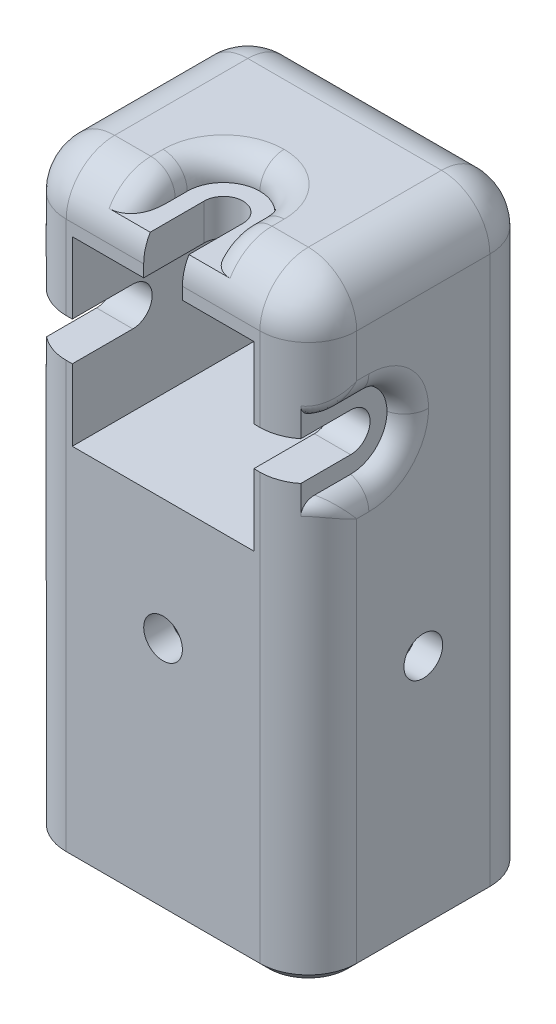
SolidWorks part; units mm, degrees
ref_plane "Front Plane" through (0, 0, 0) normal (0, 0, 1) x (1, 0, 0)
ref_plane "Top Plane" through (0, 0, 0) normal (0, 1, 0) x (1, 0, 0)
ref_plane "Right Plane" through (0, 0, 0) normal (1, 0, 0) x (0, 0, -1)
sketch "Sketch1" plane through (0, 0, 0) normal (0, 1, 0) x (1, 0, 0)
  line L1 (0, 0) -> (24, 0)
  line L2 (0, 0) -> (0, 19)
  line L3 (0, 19) -> (24, 19)
  line L4 (24, 0) -> (24, 19)
  dimension "D1" = 24
  dimension "D2" = 19
extrude "Boss-Extrude1" add sketch "Sketch1" along normal blind 50
sketch "Sketch2" plane through (0, 0, 0) normal (0, 0, 1) x (1, 0, 0)
  line L0 (0, 0) -> (24, 0) construction
  line L1 (4.5, 45) -> (19.5, 45)
  line L2 (4.5, 45) -> (4.5, 30)
  line L3 (4.5, 30) -> (19.5, 30)
  line L4 (19.5, 45) -> (19.5, 30)
  line L5 (0, 50) -> (24, 50) construction
  point P6 (12, 45)
  point P9 (12, 50)
  dimension "D1" = 15
  dimension "D2" = 30
extrude "Cut-Extrude1" cut sketch "Sketch2" against normal blind 16
sketch "Sketch3" plane through (0, 0, -16) normal (0, 0, 1) x (1, 0, 0)
  line L0 (19.5, 45) -> (4.5, 45) construction
  line L1 (19.5, 30) -> (19.5, 45) construction
  circle A0 centre (12, 37.5) radius 1.6
  point P5 (12, 45)
  point P9 (19.5, 37.5)
  dimension "D1" = 3.2
extrude "Cut-Extrude2" cut sketch "Sketch3" against normal up to next
sketch "Sketch4" plane through (0, 0, 0) normal (0, -1, 0) x (1, 0, 0)
  line L5 (0, 0) -> (24, 0) construction
  line L11 (24, 0) -> (24, -19) construction
  line L48 (24, -19) -> (0, -19) construction
  line L49 (8.95, -16.8) -> (15.05, -16.8)
  line L50 (8.95, -16.8) -> (8.95, -13.8)
  line L51 (8.95, -13.8) -> (15.05, -13.8)
  line L52 (15.05, -16.8) -> (15.05, -13.8)
  line L53 (2.2, -12.55) -> (5.2, -12.55)
  line L54 (2.2, -12.55) -> (2.2, -6.45)
  line L55 (2.2, -6.45) -> (5.2, -6.45)
  line L56 (5.2, -12.55) -> (5.2, -6.45)
  line L57 (8.95, -5.2) -> (15.05, -5.2)
  line L58 (8.95, -5.2) -> (8.95, -2.2)
  line L59 (8.95, -2.2) -> (15.05, -2.2)
  line L60 (15.05, -5.2) -> (15.05, -2.2)
  line L61 (18.8, -12.55) -> (21.8, -12.55)
  line L62 (18.8, -12.55) -> (18.8, -6.45)
  line L63 (18.8, -6.45) -> (21.8, -6.45)
  line L64 (21.8, -12.55) -> (21.8, -6.45)
  line L65 (0, -19) -> (0, 0) construction
  point P20 (12, -16.8)
  point P21 (12, -5.2)
  point P24 (12, -19)
  point P25 (2.2, -9.5)
  point P26 (18.8, -9.5)
  point P37 (24, -9.5)
  dimension "D1" = 6.1
  dimension "D2" = 3
  dimension "D3" = 2.2
  dimension "D4" = 2.2
  dimension "D5" = 2.2
  dimension "D6" = 2.2
extrude "Cut-Extrude3" cut sketch "Sketch4" against normal blind 23
sketch "Sketch5" plane through (0, 0, -19) normal (0, 0, -1) x (-1, 0, 0)
  line L0 (-24, 0) -> (0, 0) construction
  circle A0 centre (-12, 20) radius 1.6
  point P5 (-12, 0)
  dimension "D1" = 3.2
  dimension "D2" = 20
extrude "Cut-Extrude4" cut sketch "Sketch5" against normal through all
sketch "Sketch6" plane through (0, 0, 0) normal (-1, 0, 0) x (0, 0, 1)
  line L0 (-19, 0) -> (0, 0) construction
  circle A0 centre (-9.5, 20) radius 1.6
  point P5 (-9.5, 0)
  dimension "D1" = 3.2
  dimension "D2" = 20
extrude "Cut-Extrude5" cut sketch "Sketch6" against normal through all
sketch "Sketch7" plane through (0, 0, 0) normal (0, 0, 1) x (1, 0, 0)
  line L0 (0, 50) -> (0, 0) construction
  line L1 (0, 40.5) -> (1.5, 40.5)
  line L2 (0, 40.5) -> (0, 34.5)
  line L3 (0, 34.5) -> (1.5, 34.5)
  line L4 (1.5, 40.5) -> (1.5, 34.5)
  line L5 (24, 50) -> (24, 0) construction
  line L6 (24, 40.5) -> (22.5, 40.5)
  line L7 (24, 40.5) -> (24, 34.5)
  line L8 (24, 34.5) -> (22.5, 34.5)
  line L9 (22.5, 40.5) -> (22.5, 34.5)
  line L10 (0, 50) -> (24, 50) construction
  line L11 (9, 50) -> (15, 50)
  line L12 (9, 50) -> (9, 48)
  line L13 (9, 48) -> (15, 48)
  line L14 (15, 50) -> (15, 48)
  line L15 (19.5, 45) -> (4.5, 45) construction
  line L16 (4.5, 45) -> (4.5, 30) construction
  line L17 (19.5, 30) -> (19.5, 45) construction
  point P24 (22.5, 37.5)
  point P25 (19.5, 37.5)
  point P26 (1.5, 37.5)
  point P27 (4.5, 37.5)
  point P28 (12, 45)
  point P29 (12, 48)
  dimension "D1" = 3
  dimension "D2" = 3
  dimension "D3" = 3
  dimension "D4" = 6
extrude "Cut-Extrude6" cut sketch "Sketch7" against normal blind 8
sketch "Sketch8" plane through (1.5, 0, 0) normal (-1, 0, 0) x (0, 0, 1)
  line L0 (-5, 35.9) -> (0, 35.9)
  line L1 (0, 34.5) -> (0, 40.5) construction
  line L2 (0, 35.9) -> (0, 39.1)
  line L3 (0, 39.1) -> (-5, 39.1)
  arc A0 (-5, 39.1) -> (-5, 35.9) centre (-5, 37.5) ccw
  point P1 (0, 37.5)
  point P6 (0, 37.5)
  dimension "D1" = 1.6
  dimension "D2" = 5
extrude "Cut-Extrude7" cut sketch "Sketch8" against normal through all
sketch "Sketch9" plane through (0, 48, 0) normal (0, 1, 0) x (1, 0, 0)
  line L0 (10.4, 5) -> (10.4, 0)
  line L1 (9, 0) -> (15, 0) construction
  line L2 (10.4, 0) -> (13.6, 0)
  line L3 (13.6, 0) -> (13.6, 5)
  arc A0 (13.6, 5) -> (10.4, 5) centre (12, 5) ccw
  point P1 (12, 0)
  point P6 (12, 0)
  dimension "D1" = 1.6
  dimension "D2" = 5
extrude "Cut-Extrude8" cut sketch "Sketch9" against normal up to next
fillet "Fillet2" radius 3 6 edges at (23.25, 34.5, -8) (23.25, 40.5, -8) (0.75, 40.5, -8) (0.75, 34.5, -8) (15, 49, -8) (9, 49, -8)
fillet "Fillet4" radius 4 6 edges at (24, 25, -19) (0, 25, -19) (24, 17.25, 0) (0, 17.25, 0) (24, 45.25, 0) (0, 45.25, 0)
fillet "Fillet5" radius 4 9 edges at (17.5, 50, 0) (22.8284, 50, -1.1716) (24, 50, -9.5) (22.8284, 50, -17.8284) (12, 50, -19) (1.1716, 50, -17.8284) (6.5, 50, 0) (1.1716, 50, -1.1716) (0, 50, -9.5)
fillet "Fillet6" radius 2 14 edges at (24, 40.5, -4.5) (24, 34.5, -4.5) (24, 35.3787, -7.1213) (9, 49.4641, -2) (9, 50, -4.5) (9.8787, 50, -7.1213) (15, 49.4641, -2) (15, 50, -4.5) (0, 34.5, -4.5) (0, 35.3787, -7.1213) (0, 40.5, -4.5) (24, 39.6213, -7.1213) (14.1213, 50, -7.1213) (0, 39.6213, -7.1213)
fillet "Fillet7" radius 1 4 edges at (23.1739, 40.8173, -1.5656) (23.1739, 34.1827, -1.5656) (0.8261, 40.8173, -1.5656) (0.8261, 34.1827, -1.5656)
chamfer "Chamfer1" distance 0.75 angle 45 24 edges at (12, 0, 0) (22.8284, 0, -1.1716) (1.1716, 0, -1.1716) (24, 0, -9.5) (0, 0, -9.5) (22.8284, 0, -17.8284) (1.1716, 0, -17.8284) (12, 0, -19) (20.3, 0, -12.55) (21.8, 0, -9.5) (20.3, 0, -6.45) (18.8, 0, -9.5) (12, 0, -5.2) (15.05, 0, -3.7) (12, 0, -2.2) (8.95, 0, -3.7) (3.7, 0, -12.55) (5.2, 0, -9.5) (3.7, 0, -6.45) (2.2, 0, -9.5) (12, 0, -16.8) (15.05, 0, -15.3) (12, 0, -13.8) (8.95, 0, -15.3)
